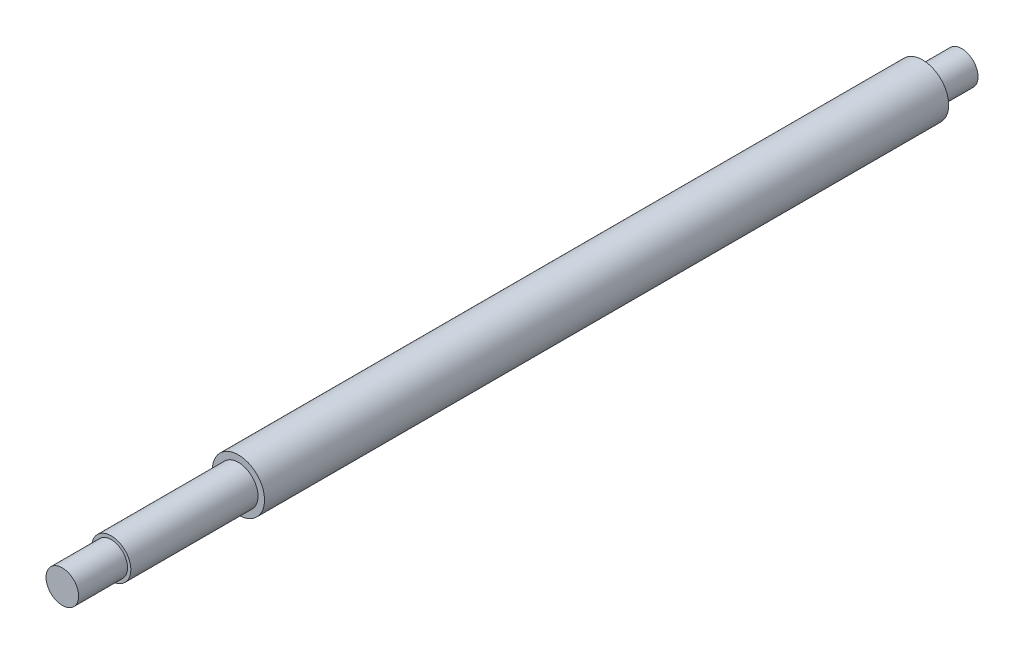
SolidWorks part; units mm, degrees
ref_plane "Front Plane" through (0, 0, 0) normal (0, 0, 1) x (1, 0, 0)
ref_plane "Top Plane" through (0, 0, 0) normal (0, 1, 0) x (1, 0, 0)
ref_plane "Right Plane" through (0, 0, 0) normal (1, 0, 0) x (0, 0, -1)
sketch "Sketch1" plane through (0, 0, 0) normal (1, 0, 0) x (0, 0, -1)
  line L0 (0, 0) -> (-42.623, 0) construction
  line L1 (-275.75, 0) -> (-275.75, 5)
  line L2 (-275.75, 5) -> (-260.75, 5)
  line L3 (-260.75, 5) -> (-260.75, 6)
  line L4 (-260.75, 6) -> (-221.75, 6)
  line L5 (-221.75, 6) -> (-221.75, 8)
  line L6 (-221.75, 8) -> (-12, 8)
  line L7 (-12, 8) -> (-12, 5)
  line L8 (-12, 5) -> (0, 5)
  line L9 (0, 5) -> (0, 0)
  line L10 (-275.75, 0) -> (0, 0)
  point P6 (0, 0)
  dimension "D1" = 5
  dimension "D2" = 6
  dimension "D3" = 8
  dimension "D4" = 5
  dimension "D5" = 12
  dimension "D6" = 39
  dimension "D7" = 15
  dimension "D8" = 209.75
revolve "Revolve1" add sketch "Sketch1" angle 360 about L0
